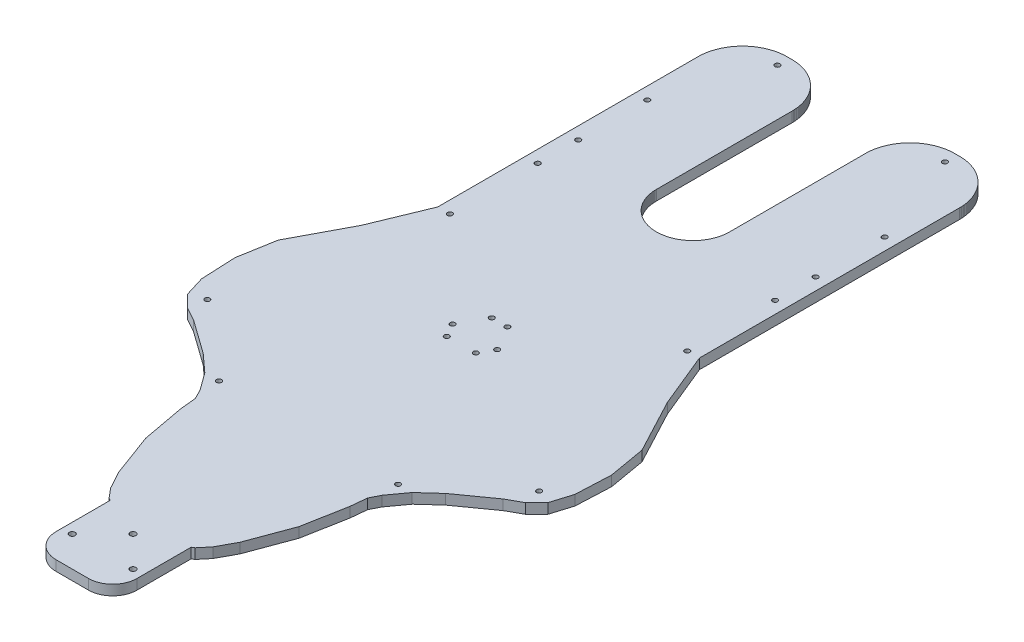
SolidWorks part; units mm, degrees
material "6061-T6 (SS)"
ref_plane "Front Plane" through (0, 0, 0) normal (0, 0, 1) x (1, 0, 0)
ref_plane "Top Plane" through (0, 0, 0) normal (0, 1, 0) x (1, 0, 0)
ref_plane "Right Plane" through (0, 0, 0) normal (1, 0, 0) x (0, 0, -1)
sketch "Sketch1" plane through (0, 0, 0) normal (0, 1, 0) x (1, 0, 0)
  line L0 (-1.4442, 328.045) -> (-2.1645, 328.102)
  line L1 (-2.1645, 328.102) -> (-2.8827, 328.181)
  line L2 (-2.8827, 328.181) -> (-3.598, 328.283)
  line L3 (-3.598, 328.283) -> (-4.3098, 328.407)
  line L4 (-4.3098, 328.407) -> (-5.0173, 328.554)
  line L5 (-5.0173, 328.554) -> (-5.7199, 328.723)
  line L6 (-5.7199, 328.723) -> (-6.4168, 328.913)
  line L7 (-6.4168, 328.913) -> (-7.1074, 329.126)
  line L8 (-7.1074, 329.126) -> (-7.791, 329.36)
  line L9 (-7.791, 329.36) -> (-8.4669, 329.615)
  line L10 (-8.4669, 329.615) -> (-9.1344, 329.892)
  line L11 (-9.1344, 329.892) -> (-9.7929, 330.189)
  line L12 (-9.7929, 330.189) -> (-10.4418, 330.507)
  line L13 (-10.4418, 330.507) -> (-11.0803, 330.845)
  line L14 (-11.0803, 330.845) -> (-11.7079, 331.203)
  line L15 (-11.7079, 331.203) -> (-12.324, 331.58)
  line L16 (-12.324, 331.58) -> (-12.9279, 331.977)
  line L17 (-12.9279, 331.977) -> (-13.5191, 332.393)
  line L18 (-13.5191, 332.393) -> (-14.0968, 332.826)
  line L19 (-14.0968, 332.826) -> (-14.6608, 333.278)
  line L20 (-14.6608, 333.278) -> (-15.2102, 333.747)
  line L21 (-15.2102, 333.747) -> (-15.7446, 334.234)
  line L22 (-15.7446, 334.234) -> (-16.2634, 334.737)
  line L23 (-16.2634, 334.737) -> (-16.7663, 335.255)
  line L24 (-16.7663, 335.255) -> (-17.2525, 335.79)
  line L25 (-17.2525, 335.79) -> (-17.7218, 336.339)
  line L26 (-17.7218, 336.339) -> (-18.1736, 336.903)
  line L27 (-18.1736, 336.903) -> (-18.6074, 337.481)
  line L28 (-18.6074, 337.481) -> (-19.0228, 338.072)
  line L29 (-19.0228, 338.072) -> (-19.4195, 338.676)
  line L30 (-19.4195, 338.676) -> (-19.7971, 339.292)
  line L31 (-19.7971, 339.292) -> (-20.155, 339.92)
  line L32 (-20.155, 339.92) -> (-20.4931, 340.558)
  line L33 (-20.4931, 340.558) -> (-20.811, 341.207)
  line L34 (-20.811, 341.207) -> (-21.1084, 341.866)
  line L35 (-21.1084, 341.866) -> (-21.3849, 342.533)
  line L36 (-21.3849, 342.533) -> (-21.6402, 343.209)
  line L37 (-21.6402, 343.209) -> (-21.8743, 343.893)
  line L38 (-21.8743, 343.893) -> (-22.0867, 344.583)
  line L39 (-22.0867, 344.583) -> (-22.2774, 345.28)
  line L40 (-22.2774, 345.28) -> (-22.4461, 345.983)
  line L41 (-22.4461, 345.983) -> (-22.5926, 346.69)
  line L42 (-22.5926, 346.69) -> (-22.7168, 347.402)
  line L43 (-22.7168, 347.402) -> (-22.8186, 348.117)
  line L44 (-22.8186, 348.117) -> (-22.8979, 348.835)
  line L45 (-22.8979, 348.835) -> (-22.9546, 349.556)
  line L46 (-22.9546, 349.556) -> (-22.9886, 350.278)
  line L47 (-22.9886, 350.278) -> (-23, 351)
  line L48 (-23, 351) -> (-23, 436)
  line L49 (-23, 436) -> (-23.0138, 436.879)
  line L50 (-23.0138, 436.879) -> (-23.0552, 437.758)
  line L51 (-23.0552, 437.758) -> (-23.1243, 438.635)
  line L52 (-23.1243, 438.635) -> (-23.2208, 439.509)
  line L53 (-23.2208, 439.509) -> (-23.3447, 440.38)
  line L54 (-23.3447, 440.38) -> (-23.496, 441.247)
  line L55 (-23.496, 441.247) -> (-23.6743, 442.108)
  line L56 (-23.6743, 442.108) -> (-23.8797, 442.963)
  line L57 (-23.8797, 442.963) -> (-24.1118, 443.812)
  line L58 (-24.1118, 443.812) -> (-24.3704, 444.652)
  line L59 (-24.3704, 444.652) -> (-24.6553, 445.485)
  line L60 (-24.6553, 445.485) -> (-24.9662, 446.307)
  line L61 (-24.9662, 446.307) -> (-25.3029, 447.12)
  line L62 (-25.3029, 447.12) -> (-25.6648, 447.922)
  line L63 (-25.6648, 447.922) -> (-26.0518, 448.712)
  line L64 (-26.0518, 448.712) -> (-26.4634, 449.489)
  line L65 (-26.4634, 449.489) -> (-26.8992, 450.253)
  line L66 (-26.8992, 450.253) -> (-27.3588, 451.003)
  line L67 (-27.3588, 451.003) -> (-27.8417, 451.738)
  line L68 (-27.8417, 451.738) -> (-28.3475, 452.458)
  line L69 (-28.3475, 452.458) -> (-28.8757, 453.161)
  line L70 (-28.8757, 453.161) -> (-29.4256, 453.848)
  line L71 (-29.4256, 453.848) -> (-29.9969, 454.517)
  line L72 (-29.9969, 454.517) -> (-30.5889, 455.167)
  line L73 (-30.5889, 455.167) -> (-31.201, 455.799)
  line L74 (-31.201, 455.799) -> (-31.8327, 456.411)
  line L75 (-31.8327, 456.411) -> (-32.4833, 457.003)
  line L76 (-32.4833, 457.003) -> (-33.1521, 457.574)
  line L77 (-33.1521, 457.574) -> (-33.8386, 458.124)
  line L78 (-33.8386, 458.124) -> (-34.542, 458.652)
  line L79 (-34.542, 458.652) -> (-35.2617, 459.158)
  line L80 (-35.2617, 459.158) -> (-35.9968, 459.641)
  line L81 (-35.9968, 459.641) -> (-36.7468, 460.101)
  line L82 (-36.7468, 460.101) -> (-37.5109, 460.537)
  line L83 (-37.5109, 460.537) -> (-38.2883, 460.948)
  line L84 (-38.2883, 460.948) -> (-39.0782, 461.335)
  line L85 (-39.0782, 461.335) -> (-39.8799, 461.697)
  line L86 (-39.8799, 461.697) -> (-40.6925, 462.034)
  line L87 (-40.6925, 462.034) -> (-41.5153, 462.345)
  line L88 (-41.5153, 462.345) -> (-42.3475, 462.63)
  line L89 (-42.3475, 462.63) -> (-43.1882, 462.888)
  line L90 (-43.1882, 462.888) -> (-44.0367, 463.12)
  line L91 (-44.0367, 463.12) -> (-44.892, 463.326)
  line L92 (-44.892, 463.326) -> (-45.7533, 463.504)
  line L93 (-45.7533, 463.504) -> (-46.6198, 463.655)
  line L94 (-46.6198, 463.655) -> (-47.4907, 463.779)
  line L95 (-47.4907, 463.779) -> (-48.365, 463.876)
  line L96 (-48.365, 463.876) -> (-49.2419, 463.945)
  line L97 (-49.2419, 463.945) -> (-50.1205, 463.986)
  line L98 (-50.1205, 463.986) -> (-51, 464)
  line L99 (-51, 464) -> (-54, 464)
  line L100 (-54, 464) -> (-54.8795, 463.986)
  line L101 (-54.8795, 463.986) -> (-55.7581, 463.945)
  line L102 (-55.7581, 463.945) -> (-56.635, 463.876)
  line L103 (-56.635, 463.876) -> (-57.5093, 463.779)
  line L104 (-57.5093, 463.779) -> (-58.3802, 463.655)
  line L105 (-58.3802, 463.655) -> (-59.2467, 463.504)
  line L106 (-59.2467, 463.504) -> (-60.108, 463.326)
  line L107 (-60.108, 463.326) -> (-60.9633, 463.12)
  line L108 (-60.9633, 463.12) -> (-61.8117, 462.888)
  line L109 (-61.8117, 462.888) -> (-62.6525, 462.63)
  line L110 (-62.6525, 462.63) -> (-63.4846, 462.345)
  line L111 (-63.4846, 462.345) -> (-64.3075, 462.034)
  line L112 (-64.3075, 462.034) -> (-65.1201, 461.697)
  line L113 (-65.1201, 461.697) -> (-65.9218, 461.335)
  line L114 (-65.9218, 461.335) -> (-66.7117, 460.948)
  line L115 (-66.7117, 460.948) -> (-67.4891, 460.537)
  line L116 (-67.4891, 460.537) -> (-68.2532, 460.101)
  line L117 (-68.2532, 460.101) -> (-69.0031, 459.641)
  line L118 (-69.0031, 459.641) -> (-69.7383, 459.158)
  line L119 (-69.7383, 459.158) -> (-70.458, 458.652)
  line L120 (-70.458, 458.652) -> (-71.1614, 458.124)
  line L121 (-71.1614, 458.124) -> (-71.8479, 457.574)
  line L122 (-71.8479, 457.574) -> (-72.5167, 457.003)
  line L123 (-72.5167, 457.003) -> (-73.1673, 456.411)
  line L124 (-73.1673, 456.411) -> (-73.799, 455.799)
  line L125 (-73.799, 455.799) -> (-74.4111, 455.167)
  line L126 (-74.4111, 455.167) -> (-75.0031, 454.517)
  line L127 (-75.0031, 454.517) -> (-75.5744, 453.848)
  line L128 (-75.5744, 453.848) -> (-76.1243, 453.161)
  line L129 (-76.1243, 453.161) -> (-76.6525, 452.458)
  line L130 (-76.6525, 452.458) -> (-77.1582, 451.738)
  line L131 (-77.1582, 451.738) -> (-77.6412, 451.003)
  line L132 (-77.6412, 451.003) -> (-78.1008, 450.253)
  line L133 (-78.1008, 450.253) -> (-78.5366, 449.489)
  line L134 (-78.5366, 449.489) -> (-78.9482, 448.712)
  line L135 (-78.9482, 448.712) -> (-79.3351, 447.922)
  line L136 (-79.3351, 447.922) -> (-79.6971, 447.12)
  line L137 (-79.6971, 447.12) -> (-80.0337, 446.307)
  line L138 (-80.0337, 446.307) -> (-80.3447, 445.485)
  line L139 (-80.3447, 445.485) -> (-80.6296, 444.652)
  line L140 (-80.6296, 444.652) -> (-80.8882, 443.812)
  line L141 (-80.8882, 443.812) -> (-81.1203, 442.963)
  line L142 (-81.1203, 442.963) -> (-81.3257, 442.108)
  line L143 (-81.3257, 442.108) -> (-81.504, 441.247)
  line L144 (-81.504, 441.247) -> (-81.6553, 440.38)
  line L145 (-81.6553, 440.38) -> (-81.7792, 439.509)
  line L146 (-81.7792, 439.509) -> (-81.8757, 438.635)
  line L147 (-81.8757, 438.635) -> (-81.9447, 437.758)
  line L148 (-81.9447, 437.758) -> (-81.9862, 436.879)
  line L149 (-81.9862, 436.879) -> (-82, 436)
  line L150 (-82, 436) -> (-82, 273)
  line L151 (-82, 273) -> (-96, 239)
  line L152 (-96, 239) -> (-114, 205)
  line L153 (-114, 205) -> (-118, 182)
  line L154 (-118, 182) -> (-117, 160)
  line L155 (-117, 160) -> (-113, 147)
  line L156 (-113, 147) -> (-106, 140)
  line L157 (-106, 140) -> (-97, 135)
  line L158 (-97, 135) -> (-76, 120)
  line L159 (-76, 120) -> (-65, 110)
  line L160 (-65, 110) -> (-57, 99)
  line L161 (-57, 99) -> (-54, 93)
  line L162 (-54, 93) -> (-53, 83)
  line L163 (-53, 83) -> (-48, 56)
  line L164 (-48, 56) -> (-38, 29)
  line L165 (-38, 29) -> (-32, 18)
  line L166 (-32, 18) -> (-27, 12)
  line L167 (-27, 12) -> (-19, 7)
  line L168 (-19, 7) -> (-11, 3)
  line L169 (-11, 3) -> (-5, 1)
  line L170 (-5, 1) -> (0, 0)
  line L171 (0, 0) -> (5, 1)
  line L172 (5, 1) -> (11, 3)
  line L173 (11, 3) -> (19, 7)
  line L174 (19, 7) -> (27, 12)
  line L175 (27, 12) -> (32, 18)
  line L176 (32, 18) -> (38, 29)
  line L177 (38, 29) -> (48, 56)
  line L178 (48, 56) -> (53, 83)
  line L179 (53, 83) -> (54, 93)
  line L180 (54, 93) -> (57, 99)
  line L181 (57, 99) -> (65, 110)
  line L182 (65, 110) -> (76, 120)
  line L183 (76, 120) -> (97, 135)
  line L184 (97, 135) -> (106, 140)
  line L185 (106, 140) -> (113, 147)
  line L186 (113, 147) -> (117, 160)
  line L187 (117, 160) -> (118, 182)
  line L188 (118, 182) -> (114, 205)
  line L189 (114, 205) -> (96, 239)
  line L190 (96, 239) -> (82, 273)
  line L191 (82, 273) -> (82, 436)
  line L192 (82, 436) -> (81.9862, 436.879)
  line L193 (81.9862, 436.879) -> (81.9447, 437.758)
  line L194 (81.9447, 437.758) -> (81.8757, 438.635)
  line L195 (81.8757, 438.635) -> (81.7792, 439.509)
  line L196 (81.7792, 439.509) -> (81.6553, 440.38)
  line L197 (81.6553, 440.38) -> (81.504, 441.247)
  line L198 (81.504, 441.247) -> (81.3257, 442.108)
  line L199 (81.3257, 442.108) -> (81.1203, 442.963)
  line L200 (81.1203, 442.963) -> (80.8882, 443.812)
  line L201 (80.8882, 443.812) -> (80.6296, 444.652)
  line L202 (80.6296, 444.652) -> (80.3447, 445.485)
  line L203 (80.3447, 445.485) -> (80.0337, 446.307)
  line L204 (80.0337, 446.307) -> (79.6971, 447.12)
  line L205 (79.6971, 447.12) -> (79.3351, 447.922)
  line L206 (79.3351, 447.922) -> (78.9482, 448.712)
  line L207 (78.9482, 448.712) -> (78.5366, 449.489)
  line L208 (78.5366, 449.489) -> (78.1008, 450.253)
  line L209 (78.1008, 450.253) -> (77.6412, 451.003)
  line L210 (77.6412, 451.003) -> (77.1582, 451.738)
  line L211 (77.1582, 451.738) -> (76.6525, 452.458)
  line L212 (76.6525, 452.458) -> (76.1243, 453.161)
  line L213 (76.1243, 453.161) -> (75.5744, 453.848)
  line L214 (75.5744, 453.848) -> (75.0031, 454.517)
  line L215 (75.0031, 454.517) -> (74.4111, 455.167)
  line L216 (74.4111, 455.167) -> (73.799, 455.799)
  line L217 (73.799, 455.799) -> (73.1673, 456.411)
  line L218 (73.1673, 456.411) -> (72.5167, 457.003)
  line L219 (72.5167, 457.003) -> (71.8479, 457.574)
  line L220 (71.8479, 457.574) -> (71.1614, 458.124)
  line L221 (71.1614, 458.124) -> (70.458, 458.652)
  line L222 (70.458, 458.652) -> (69.7383, 459.158)
  line L223 (69.7383, 459.158) -> (69.0031, 459.641)
  line L224 (69.0031, 459.641) -> (68.2532, 460.101)
  line L225 (68.2532, 460.101) -> (67.4891, 460.537)
  line L226 (67.4891, 460.537) -> (66.7117, 460.948)
  line L227 (66.7117, 460.948) -> (65.9218, 461.335)
  line L228 (65.9218, 461.335) -> (65.1201, 461.697)
  line L229 (65.1201, 461.697) -> (64.3075, 462.034)
  line L230 (64.3075, 462.034) -> (63.4846, 462.345)
  line L231 (63.4846, 462.345) -> (62.6525, 462.63)
  line L232 (62.6525, 462.63) -> (61.8117, 462.888)
  line L233 (61.8117, 462.888) -> (60.9633, 463.12)
  line L234 (60.9633, 463.12) -> (60.108, 463.326)
  line L235 (60.108, 463.326) -> (59.2467, 463.504)
  line L236 (59.2467, 463.504) -> (58.3802, 463.655)
  line L237 (58.3802, 463.655) -> (57.5093, 463.779)
  line L238 (57.5093, 463.779) -> (56.635, 463.876)
  line L239 (56.635, 463.876) -> (55.7581, 463.945)
  line L240 (55.7581, 463.945) -> (54.8795, 463.986)
  line L241 (54.8795, 463.986) -> (54, 464)
  line L242 (54, 464) -> (51, 464)
  line L243 (51, 464) -> (50.1205, 463.986)
  line L244 (50.1205, 463.986) -> (49.2419, 463.945)
  line L245 (49.2419, 463.945) -> (48.365, 463.876)
  line L246 (48.365, 463.876) -> (47.4907, 463.779)
  line L247 (47.4907, 463.779) -> (46.6198, 463.655)
  line L248 (46.6198, 463.655) -> (45.7533, 463.504)
  line L249 (45.7533, 463.504) -> (44.892, 463.326)
  line L250 (44.892, 463.326) -> (44.0367, 463.12)
  line L251 (44.0367, 463.12) -> (43.1882, 462.888)
  line L252 (43.1882, 462.888) -> (42.3475, 462.63)
  line L253 (42.3475, 462.63) -> (41.5153, 462.345)
  line L254 (41.5153, 462.345) -> (40.6925, 462.034)
  line L255 (40.6925, 462.034) -> (39.8799, 461.697)
  line L256 (39.8799, 461.697) -> (39.0782, 461.335)
  line L257 (39.0782, 461.335) -> (38.2883, 460.948)
  line L258 (38.2883, 460.948) -> (37.5109, 460.537)
  line L259 (37.5109, 460.537) -> (36.7468, 460.101)
  line L260 (36.7468, 460.101) -> (35.9968, 459.641)
  line L261 (35.9968, 459.641) -> (35.2617, 459.158)
  line L262 (35.2617, 459.158) -> (34.542, 458.652)
  line L263 (34.542, 458.652) -> (33.8386, 458.124)
  line L264 (33.8386, 458.124) -> (33.1521, 457.574)
  line L265 (33.1521, 457.574) -> (32.4833, 457.003)
  line L266 (32.4833, 457.003) -> (31.8327, 456.411)
  line L267 (31.8327, 456.411) -> (31.201, 455.799)
  line L268 (31.201, 455.799) -> (30.5889, 455.167)
  line L269 (30.5889, 455.167) -> (29.9969, 454.517)
  line L270 (29.9969, 454.517) -> (29.4256, 453.848)
  line L271 (29.4256, 453.848) -> (28.8757, 453.161)
  line L272 (28.8757, 453.161) -> (28.3475, 452.458)
  line L273 (28.3475, 452.458) -> (27.8417, 451.738)
  line L274 (27.8417, 451.738) -> (27.3588, 451.003)
  line L275 (27.3588, 451.003) -> (26.8992, 450.253)
  line L276 (26.8992, 450.253) -> (26.4634, 449.489)
  line L277 (26.4634, 449.489) -> (26.0518, 448.712)
  line L278 (26.0518, 448.712) -> (25.6648, 447.922)
  line L279 (25.6648, 447.922) -> (25.3029, 447.12)
  line L280 (25.3029, 447.12) -> (24.9662, 446.307)
  line L281 (24.9662, 446.307) -> (24.6553, 445.485)
  line L282 (24.6553, 445.485) -> (24.3704, 444.652)
  line L283 (24.3704, 444.652) -> (24.1118, 443.812)
  line L284 (24.1118, 443.812) -> (23.8797, 442.963)
  line L285 (23.8797, 442.963) -> (23.6743, 442.108)
  line L286 (23.6743, 442.108) -> (23.496, 441.247)
  line L287 (23.496, 441.247) -> (23.3447, 440.38)
  line L288 (23.3447, 440.38) -> (23.2208, 439.509)
  line L289 (23.2208, 439.509) -> (23.1243, 438.635)
  line L290 (23.1243, 438.635) -> (23.0552, 437.758)
  line L291 (23.0552, 437.758) -> (23.0138, 436.879)
  line L292 (23.0138, 436.879) -> (23, 436)
  line L293 (23, 436) -> (23, 351)
  line L294 (23, 351) -> (22.9886, 350.278)
  line L295 (22.9886, 350.278) -> (22.9546, 349.556)
  line L296 (22.9546, 349.556) -> (22.8979, 348.835)
  line L297 (22.8979, 348.835) -> (22.8186, 348.117)
  line L298 (22.8186, 348.117) -> (22.7168, 347.402)
  line L299 (22.7168, 347.402) -> (22.5926, 346.69)
  line L300 (22.5926, 346.69) -> (22.4461, 345.983)
  line L301 (22.4461, 345.983) -> (22.2774, 345.28)
  line L302 (22.2774, 345.28) -> (22.0867, 344.583)
  line L303 (22.0867, 344.583) -> (21.8743, 343.893)
  line L304 (21.8743, 343.893) -> (21.6402, 343.209)
  line L305 (21.6402, 343.209) -> (21.3849, 342.533)
  line L306 (21.3849, 342.533) -> (21.1084, 341.866)
  line L307 (21.1084, 341.866) -> (20.811, 341.207)
  line L308 (20.811, 341.207) -> (20.4931, 340.558)
  line L309 (20.4931, 340.558) -> (20.155, 339.92)
  line L310 (20.155, 339.92) -> (19.7971, 339.292)
  line L311 (19.7971, 339.292) -> (19.4195, 338.676)
  line L312 (19.4195, 338.676) -> (19.0228, 338.072)
  line L313 (19.0228, 338.072) -> (18.6074, 337.481)
  line L314 (18.6074, 337.481) -> (18.1736, 336.903)
  line L315 (18.1736, 336.903) -> (17.7218, 336.339)
  line L316 (17.7218, 336.339) -> (17.2525, 335.79)
  line L317 (17.2525, 335.79) -> (16.7663, 335.255)
  line L318 (16.7663, 335.255) -> (16.2634, 334.737)
  line L319 (16.2634, 334.737) -> (15.7446, 334.234)
  line L320 (15.7446, 334.234) -> (15.2102, 333.747)
  line L321 (15.2102, 333.747) -> (14.6608, 333.278)
  line L322 (14.6608, 333.278) -> (14.0968, 332.826)
  line L323 (14.0968, 332.826) -> (13.5191, 332.393)
  line L324 (13.5191, 332.393) -> (12.9279, 331.977)
  line L325 (12.9279, 331.977) -> (12.324, 331.58)
  line L326 (12.324, 331.58) -> (11.7079, 331.203)
  line L327 (11.7079, 331.203) -> (11.0803, 330.845)
  line L328 (11.0803, 330.845) -> (10.4418, 330.507)
  line L329 (10.4418, 330.507) -> (9.7929, 330.189)
  line L330 (9.7929, 330.189) -> (9.1344, 329.892)
  line L331 (9.1344, 329.892) -> (8.4669, 329.615)
  line L332 (8.4669, 329.615) -> (7.791, 329.36)
  line L333 (7.791, 329.36) -> (7.1074, 329.126)
  line L334 (7.1074, 329.126) -> (6.4168, 328.913)
  line L335 (6.4168, 328.913) -> (5.7199, 328.723)
  line L336 (5.7199, 328.723) -> (5.0173, 328.554)
  line L337 (5.0173, 328.554) -> (4.3098, 328.407)
  line L338 (4.3098, 328.407) -> (3.598, 328.283)
  line L339 (3.598, 328.283) -> (2.8827, 328.181)
  line L340 (2.8827, 328.181) -> (2.1645, 328.102)
  line L341 (2.1645, 328.102) -> (1.4442, 328.045)
  line L342 (1.4442, 328.045) -> (0.7224, 328.011)
  line L343 (0.7224, 328.011) -> (0, 328)
  line L344 (0, 328) -> (-0.7224, 328.011)
  line L345 (-0.7224, 328.011) -> (-1.4442, 328.045)
extrude "Boss-Extrude1" add sketch "Sketch1" along normal blind 6.35
ref_axis "Axis1" through (-117, 6.35, -160) along (1, 0, 0)
ref_plane "plane_aft_cg" through (0, 0, -160) normal (0, 0, 1) x (1, 0, 0)
ref_axis "Axis2" through (0, 6.35, -328) along (0, 0, 1)
ref_plane "Plane3" through (0, 0, 0) normal (-1, 0, 0) x (0, 0, 1)
ref_axis "Axis3" through (-82, 6.35, -273) along (1, 0, 0)
ref_plane "plane_fore_cg" through (0, 0, -273) normal (0, 0, 1) x (1, 0, 0)
ref_plane "plane_design_cg" through (0, 0, -216.5) normal (0, 0, 1) x (1, 0, 0)
sketch "Sketch2" plane through (0, 0, 0) normal (0, -1, 0) x (1, 0, 0)
  line L0 (0, 0) -> (0, 14.1955) construction
  line L1 (0, 18.0958) -> (0, -18.0958) construction
  line L2 (-7.9998, 0) -> (16.638, 0) construction
  line L4 (-25.4, -38.1) -> (25.4, -38.1)
  line L5 (-25.4, -38.1) -> (-25.4, 38.1)
  line L6 (-25.4, 38.1) -> (25.4, 38.1)
  line L7 (25.4, -38.1) -> (25.4, 38.1)
  dimension "D1" = 25.4
  dimension "D2" = 50.8
  dimension "D3" = 38.1
  dimension "D4" = 38.1
extrude "perineum_support" add sketch "Sketch2" against normal blind 6.35
sketch "Sketch3" plane through (0, 6.35, 0) normal (0, 1, 0) x (1, 0, 0)
  line L0 (25.4, -38.1) -> (-115.6708, -38.1) construction
  line L1 (-118.8537, 0) -> (76.5765, 0) construction
  line L2 (0, -59.3586) -> (0, 37.5588) construction
  line L3 (0, 18.0958) -> (0, -18.0958) construction
  line L4 (60.9754, -17.0766) -> (60.5369, -19.05) construction
  line L5 (60.5369, -19.05) -> (-65.1049, -19.05) construction
  circle A0 centre (19.05, -19.05) radius 1.8288
  circle A1 centre (-19.05, -19.05) radius 1.8288
  circle A2 centre (0, 0) radius 1.8288
  dimension "D3" = 3.6576
  dimension "D4" = 3.6576
  dimension "D5" = 3.6576
  dimension "D1" = 38.1
  dimension "D2" = 19.05
  dimension "D6" = 19.05
  dimension "D7" = 19.05
extrude "holes_perineum_support_bracket" cut sketch "Sketch3" against normal blind 6.35
sketch "Sketch4" plane through (0, 6.35, 0) normal (0, 1, 0) x (1, 0, 0)
  line L0 (-107.7476, 216.5) -> (107.9118, 216.5) construction
  line L1 (-21.7004, 216.5) -> (21.7004, 216.5) construction
  line L2 (114, 205) -> (96, 239) construction
  line L3 (0, 328.6691) -> (0, -81.9247) construction
  line L4 (0, 18.0958) -> (0, -18.0958) construction
  line L5 (0, 328) -> (0, 0) construction
  line L6 (0.0821, 216.5) -> (11.8173, 248.7422) construction
  circle A0 centre (0.0821, 216.5) radius 14.1 construction
  circle A1 centre (4.9046, 229.7497) radius 1.575
  circle A2 centre (-4.9046, 229.7497) radius 1.575
  circle A3 centre (9.1454, 205.6988) radius 1.575
  circle A4 centre (14.0499, 214.1937) radius 1.575
  circle A5 centre (-13.8037, 214.0516) radius 1.575
  circle A6 centre (-8.8992, 205.5566) radius 1.575
  point P20 (0.0821, 216.5)
  point P31 (0.0821, 216.5)
  dimension "D1" = 28.2
  dimension "D3" = 3.15
  dimension "D2" = 20
  dimension "D4" = 3
extrude "holes_FT_sensor" cut sketch "Sketch4" against normal blind 6.35
fillet "Fillet1" radius 15.24 2 edges at (25.4, 3.175, 38.1) (-25.4, 3.175, 38.1)
sketch "Sketch5" plane through (0, 6.35, 0) normal (0, 1, 0) x (1, 0, 0)
  line L0 (52.5, 464) -> (200.3983, 464) construction
  line L1 (54, 464) -> (51, 464) construction
  line L2 (82, 448.6627) -> (82, 249.9637) construction
  line L3 (52.5, 464) -> (52.5, 426.4524) construction
  line L4 (0, 328.0099) -> (131.6812, 328.0099) construction
  line L5 (0, 18.0958) -> (0, -18.0958) construction
  line L6 (0, 328) -> (0, 0) construction
  line L7 (-21.509, 273) -> (21.509, 273) construction
  line L8 (109.5, 143.5) -> (83.451, 176.6229) construction
  line L9 (106, 140) -> (113, 147) construction
  line L10 (40.6416, 110) -> (93.2778, 110) construction
  circle A1 centre (52.5, 456.38) radius 1.5875
  circle A2 centre (74.38, 396.69) radius 1.5875
  circle A3 centre (74.38, 328.0099) radius 1.5875
  circle A4 centre (74.38, 273) radius 1.5875
  circle A5 centre (103.9653, 150.5377) radius 1.5875
  circle A6 centre (56.11, 110) radius 1.5875
  circle A7 centre (74.38, 353.4099) radius 1.5875
  circle A8 centre (-56.11, 110) radius 1.5875
  circle A9 centre (-103.9653, 150.5377) radius 1.5875
  circle A10 centre (-74.38, 273) radius 1.5875
  circle A11 centre (-74.38, 328.0099) radius 1.5875
  circle A12 centre (-74.38, 353.4099) radius 1.5875
  circle A13 centre (-74.38, 396.69) radius 1.5875
  circle A14 centre (-52.5, 456.38) radius 1.5875
  dimension "D1" = 7.62
  dimension "D5" = 3.175
  dimension "D6" = 3.175
  dimension "D7" = 3.175
  dimension "D8" = 3.175
  dimension "D11" = 3.175
  dimension "D12" = 3.175
  dimension "D14" = 3.175
  dimension "D2" = 7.62
  dimension "D3" = 7.62
  dimension "D4" = 7.62
  dimension "D9" = 67.31
  dimension "D10" = 8.89
  dimension "D13" = 8.89
  dimension "D15" = 7.62
  dimension "D16" = 25.4
extrude "holes_snap_buttons" cut sketch "Sketch5" against normal blind 25.4
